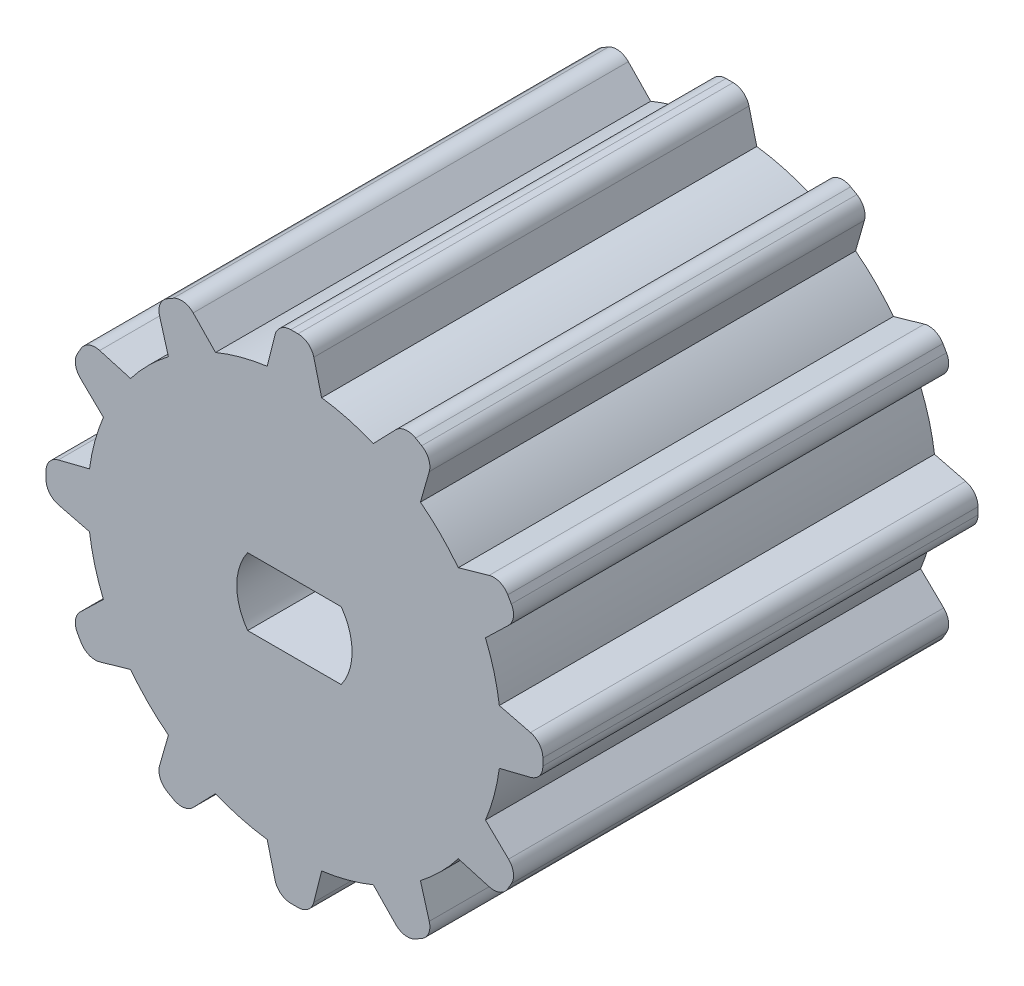
SolidWorks part; units mm, degrees
ref_plane "Ön Düzlem" through (0, 0, 0) normal (0, 0, 1) x (1, 0, 0)
ref_plane "Üst Düzlem" through (0, 0, 0) normal (0, 1, 0) x (1, 0, 0)
ref_plane "Sağ Düzlem" through (0, 0, 0) normal (1, 0, 0) x (0, 0, -1)
sketch "Çizim1" plane through (0, 0, 0) normal (0, 0, 1) x (1, 0, 0)
  line L0 (-1.25, 9.4174) -> (-0.892, 10.8493)
  line L1 (-0.1644, 11.4174) -> (0.1644, 11.4174)
  line L2 (0.892, 10.8493) -> (1.25, 9.4174)
  line L3 (3.6262, 8.7807) -> (4.6521, 9.8418)
  line L4 (5.5663, 9.97) -> (5.8511, 9.8056)
  line L5 (6.1972, 8.9498) -> (5.7912, 7.5307)
  line L6 (7.5307, 5.7912) -> (8.9498, 6.1972)
  line L7 (9.8056, 5.8511) -> (9.97, 5.5663)
  line L8 (9.8418, 4.6521) -> (8.7807, 3.6262)
  line L9 (9.4174, 1.25) -> (10.8493, 0.892)
  line L10 (11.4174, 0.1644) -> (11.4174, -0.1644)
  line L11 (10.8493, -0.892) -> (9.4174, -1.25)
  line L12 (8.7807, -3.6262) -> (9.8418, -4.6521)
  line L13 (9.97, -5.5663) -> (9.8056, -5.8511)
  line L14 (8.9498, -6.1972) -> (7.5307, -5.7912)
  line L15 (5.7912, -7.5307) -> (6.1972, -8.9498)
  line L16 (5.8511, -9.8056) -> (5.5663, -9.97)
  line L17 (4.6521, -9.8418) -> (3.6262, -8.7807)
  line L18 (1.25, -9.4174) -> (0.892, -10.8493)
  line L19 (0.1644, -11.4174) -> (-0.1644, -11.4174)
  line L20 (-0.892, -10.8493) -> (-1.25, -9.4174)
  line L21 (-3.6262, -8.7807) -> (-4.6521, -9.8418)
  line L22 (-5.5663, -9.97) -> (-5.8511, -9.8056)
  line L23 (-6.1972, -8.9498) -> (-5.7912, -7.5307)
  line L24 (-7.5307, -5.7912) -> (-8.9498, -6.1972)
  line L25 (-9.8056, -5.8511) -> (-9.97, -5.5663)
  line L26 (-9.8418, -4.6521) -> (-8.7807, -3.6262)
  line L27 (-9.4174, -1.25) -> (-10.8493, -0.892)
  line L28 (-11.4174, -0.1644) -> (-11.4174, 0.1644)
  line L29 (-10.8493, 0.892) -> (-9.4174, 1.25)
  line L30 (-8.7807, 3.6262) -> (-9.8418, 4.6521)
  line L31 (-9.97, 5.5663) -> (-9.8056, 5.8511)
  line L32 (-8.9498, 6.1972) -> (-7.5307, 5.7912)
  line L33 (-5.7912, 7.5307) -> (-6.1972, 8.9498)
  line L34 (-5.8511, 9.8056) -> (-5.5663, 9.97)
  line L35 (-4.6521, 9.8418) -> (-3.6262, 8.7807)
  arc A0 (-5.7912, 7.5307) -> (-7.5307, 5.7912) centre (0, 0) ccw
  arc A1 (-8.7807, 3.6262) -> (-9.4174, 1.25) centre (0, 0) ccw
  arc A2 (-9.4174, -1.25) -> (-8.7807, -3.6262) centre (0, 0) ccw
  arc A3 (3.6262, 8.7807) -> (1.25, 9.4174) centre (0, 0) ccw
  arc A4 (-1.25, 9.4174) -> (-3.6262, 8.7807) centre (0, 0) ccw
  arc A5 (7.5307, 5.7912) -> (5.7912, 7.5307) centre (0, 0) ccw
  arc A6 (9.4174, 1.25) -> (8.7807, 3.6262) centre (0, 0) ccw
  arc A7 (8.7807, -3.6262) -> (9.4174, -1.25) centre (0, 0) ccw
  arc A8 (5.7912, -7.5307) -> (7.5307, -5.7912) centre (0, 0) ccw
  arc A9 (1.25, -9.4174) -> (3.6262, -8.7807) centre (0, 0) ccw
  arc A10 (-3.6262, -8.7807) -> (-1.25, -9.4174) centre (0, 0) ccw
  arc A11 (-7.5307, -5.7912) -> (-5.7912, -7.5307) centre (0, 0) ccw
  arc A12 (0.1644, 11.4174) -> (0.892, 10.8493) centre (0.1644, 10.6674) cw
  arc A13 (-0.892, 10.8493) -> (-0.1644, 11.4174) centre (-0.1644, 10.6674) cw
  arc A14 (9.8418, -4.6521) -> (9.97, -5.5663) centre (9.3205, -5.1913) cw
  arc A15 (9.8056, -5.8511) -> (8.9498, -6.1972) centre (9.156, -5.4761) cw
  arc A16 (6.1972, -8.9498) -> (5.8511, -9.8056) centre (5.4761, -9.156) cw
  arc A17 (5.5663, -9.97) -> (4.6521, -9.8418) centre (5.1913, -9.3205) cw
  arc A18 (0.892, -10.8493) -> (0.1644, -11.4174) centre (0.1644, -10.6674) cw
  arc A19 (-0.1644, -11.4174) -> (-0.892, -10.8493) centre (-0.1644, -10.6674) cw
  arc A20 (-4.6521, -9.8418) -> (-5.5663, -9.97) centre (-5.1913, -9.3205) cw
  arc A21 (-5.8511, -9.8056) -> (-6.1972, -8.9498) centre (-5.4761, -9.156) cw
  arc A22 (-8.9498, -6.1972) -> (-9.8056, -5.8511) centre (-9.156, -5.4761) cw
  arc A23 (-9.97, -5.5663) -> (-9.8418, -4.6521) centre (-9.3205, -5.1913) cw
  arc A24 (-10.8493, -0.892) -> (-11.4174, -0.1644) centre (-10.6674, -0.1644) cw
  arc A25 (-11.4174, 0.1644) -> (-10.8493, 0.892) centre (-10.6674, 0.1644) cw
  arc A26 (-9.8418, 4.6521) -> (-9.97, 5.5663) centre (-9.3205, 5.1913) cw
  arc A27 (-9.8056, 5.8511) -> (-8.9498, 6.1972) centre (-9.156, 5.4761) cw
  arc A28 (-6.1972, 8.9498) -> (-5.8511, 9.8056) centre (-5.4761, 9.156) cw
  arc A29 (-5.5663, 9.97) -> (-4.6521, 9.8418) centre (-5.1913, 9.3205) cw
  arc A30 (11.4174, -0.1644) -> (10.8493, -0.892) centre (10.6674, -0.1644) cw
  arc A31 (10.8493, 0.892) -> (11.4174, 0.1644) centre (10.6674, 0.1644) cw
  arc A32 (9.97, 5.5663) -> (9.8418, 4.6521) centre (9.3205, 5.1913) cw
  arc A33 (8.9498, 6.1972) -> (9.8056, 5.8511) centre (9.156, 5.4761) cw
  arc A34 (5.8511, 9.8056) -> (6.1972, 8.9498) centre (5.4761, 9.156) cw
  arc A35 (4.6521, 9.8418) -> (5.5663, 9.97) centre (5.1913, 9.3205) cw
  point P9 (0.75, 11.4174)
  point P53 (0, 0)
  point P56 (-0.75, 11.4174)
  dimension "D1" = 19
  dimension "D6" = 0.75
  dimension "D7" = 0.75
  dimension "D2" = 2.5
  dimension "D3" = 1.5
  dimension "D4" = 2
  dimension "D5" = 12
extrude "Yükseklik-Ekstrüzyon1" add sketch "Çizim1" against normal blind 20
sketch "Çizim2" plane through (0, 0, -20) normal (0, 0, -1) x (-1, 0, 0)
  circle A0 centre (0, 0) radius 5
  dimension "D1" = 10
extrude "Kes-Ekstrüzyon1" cut sketch "Çizim2" against normal blind 15
sketch "Çizim3" plane through (0, 0, -20) normal (0, 0, -1) x (-1, 0, 0)
  line L0 (-2.1541, 2.5) -> (2.1541, 2.5)
  arc A0 (-2.1541, 2.5) -> (2.1541, 2.5) centre (0, 0) ccw
  circle A1 centre (0, 0) radius 7.4333
  dimension "D1" = 6.6
  dimension "D2" = 2.5
extrude "Yükseklik-Ekstrüzyon2" add sketch "Çizim3" against normal blind 15
extrude "Yükseklik-Ekstrüzyon3" add sketch "Çizim1<2>" against normal blind 20
sketch "Çizim1<2>" plane through (0, 0, 0) normal (0, 0, 1) x (1, 0, 0) same geometry as "Çizim1"
sketch "Çizim4" plane through (0, 0, 0) normal (0, 0, 1) x (1, 0, 0)
  line L0 (-2.1494, 1.55) -> (2.1494, 1.55)
  line L1 (-2.1494, -1.55) -> (2.1494, -1.55)
  arc A0 (-2.1494, 1.55) -> (-2.1494, -1.55) centre (0, 0) ccw
  arc A1 (2.1494, -1.55) -> (2.1494, 1.55) centre (0, 0) ccw
  dimension "D1" = 5.3
  dimension "D2" = 3.1
extrude "Kes-Ekstrüzyon2" cut sketch "Çizim4" against normal blind 20
